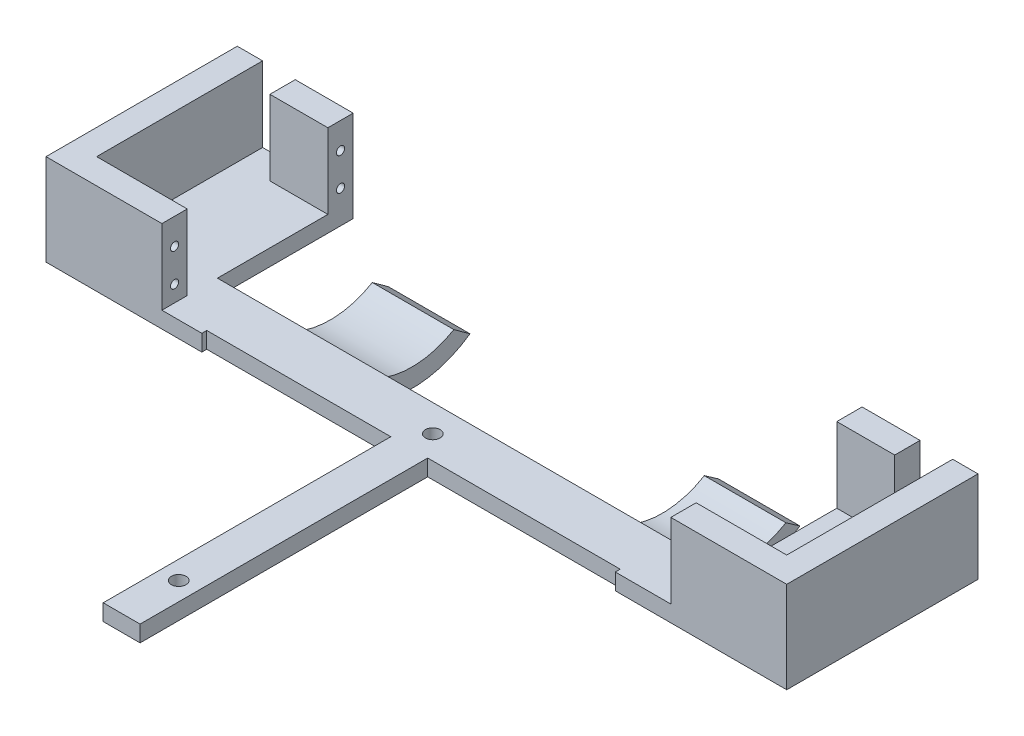
SolidWorks part; units mm, degrees
material "ABS"
ref_plane "Front" through (0, 0, 0) normal (0, 0, 1) x (1, 0, 0)
ref_plane "Top" through (0, 0, 0) normal (0, 1, 0) x (1, 0, 0)
ref_plane "Right" through (0, 0, 0) normal (1, 0, 0) x (0, 0, -1)
sketch "Sketch5" plane through (0, 0, 0) normal (0, 1, 0) x (1, 0, 0)
  line L0 (0, 0) -> (0, 88.14)
  line L1 (0, 88.14) -> (-56.41, 88.14)
  line L2 (-56.41, 88.14) -> (-56.41, 86.64)
  line L3 (-56.41, 86.64) -> (-96.41, 86.64)
  line L4 (-96.41, 86.64) -> (-96.41, 145.26)
  line L5 (-96.41, 145.26) -> (-56.41, 145.26)
  line L6 (-56.41, 145.26) -> (-56.41, 103.66)
  line L7 (-56.41, 103.66) -> (9.075, 103.66)
  line L10 (0, 0) -> (11.3, 0)
  line L11 (11.3, 0) -> (11.3, 88.14)
  line L12 (11.3, 88.14) -> (70.3, 88.14)
  line L13 (70.3, 88.14) -> (70.3, 86.64)
  line L14 (70.3, 86.64) -> (115.07, 86.64)
  line L15 (115.07, 86.64) -> (115.07, 145.26)
  line L16 (115.07, 145.26) -> (70.3, 145.26)
  line L17 (70.3, 145.26) -> (70.3, 103.66)
  line L18 (70.3, 103.66) -> (9.075, 103.66)
  dimension "D2" = 88.14
  dimension "D3" = 40
  dimension "D4" = 58.62
  dimension "D5" = 15.52
  dimension "D6" = 1.5
  dimension "D7" = 59
  dimension "D8" = 44.77
  dimension "D9" = 58.62
  dimension "D10" = 1.5
  dimension "D11" = 11.3
  dimension "D12" = 56.41
extrude "Boss-Extrude1" add sketch "Sketch5" along normal blind 5
sketch "Sketch6" plane through (0, 5, 0) normal (0, 1, 0) x (1, 0, 0)
  line L0 (-96.41, 137.5) -> (-94.6, 137.5)
  line L1 (-96.41, 145.26) -> (-96.41, 86.64) construction
  line L2 (-94.6, 137.5) -> (-94.6, 145.26)
  line L3 (-56.41, 145.26) -> (-96.41, 145.26) construction
  line L4 (-94.6, 145.26) -> (-96.41, 145.26)
  line L5 (-96.41, 145.26) -> (-96.41, 137.5)
  line L6 (-87.41, 145.26) -> (-87.41, 137.5)
  line L7 (-87.41, 137.5) -> (-68.65, 137.5)
  line L9 (-68.65, 137.5) -> (-68.65, 145.26)
  line L10 (-68.65, 145.26) -> (-87.41, 145.26)
  point P14 (-94.6, 141.38)
  dimension "D1" = 7.76
  dimension "D2" = 1.81
  dimension "D3" = 7.19
  dimension "D4" = 18.76
  dimension "D5" = 7.76
extrude "Boss-Extrude2" add sketch "Sketch6" along normal blind 28
sketch "Sketch7" plane through (-94.6, 0, 0) normal (1, 0, 0) x (0, 0, -1)
  line L0 (145.26, 33) -> (145.26, 5) construction
  line L1 (137.5, 33) -> (145.26, 33)
  line L2 (137.5, 33) -> (137.5, 28)
  line L3 (137.5, 28) -> (145.26, 28)
  line L4 (145.26, 33) -> (145.26, 28)
  dimension "D1" = 5
extrude "Boss-Extrude3" add sketch "Sketch7" along normal up to next
sketch "Sketch9" plane through (0, 0, -145.26) normal (0, 0, -1) x (-1, 0, 0)
  line L0 (96.41, 33) -> (96.41, 0) construction
  line L1 (68.65, 33) -> (96.41, 33)
  line L2 (68.65, 33) -> (68.65, 28)
  line L3 (68.65, 28) -> (96.41, 28)
  line L4 (96.41, 33) -> (96.41, 28)
extrude "Boss-Extrude4" add sketch "Sketch9" against normal up to surface (58.62 mm away) up to face at (-76.41, 2.5, -86.64)
sketch "Sketch10" plane through (0, 28, 0) normal (0, -1, 0) x (1, 0, 0)
  line L0 (-68.65, -86.64) -> (-68.65, -137.5) construction
  line L1 (-96.41, -86.64) -> (-68.65, -86.64)
  line L2 (-96.41, -86.64) -> (-96.41, -94.4)
  line L3 (-96.41, -94.4) -> (-68.65, -94.4)
  line L4 (-68.65, -86.64) -> (-68.65, -94.4)
  dimension "D1" = 7.76
extrude "Boss-Extrude5" add sketch "Sketch10" along normal up to next
sketch "Sketch11" plane through (-96.41, 0, 0) normal (-1, 0, 0) x (0, 0, 1)
  line L1 (-86.64, 0) -> (-145.26, 0)
  line L2 (-86.64, 0) -> (-86.64, 33)
  line L3 (-86.64, 33) -> (-145.26, 33)
  line L4 (-145.26, 0) -> (-145.26, 33)
extrude "Boss-Extrude6" add sketch "Sketch11" along normal blind 7.76
sketch "Sketch12" plane through (0, 5, 0) normal (0, 1, 0) x (1, 0, 0)
  line L0 (0, 0) -> (11.3, 0) construction
  line L1 (0, 88.14) -> (0, 0) construction
  circle A0 centre (5.65, 17.48) radius 2.25
  circle A1 centre (5.65, 95.35) radius 2.25
  dimension "D1" = 4.5
  dimension "D2" = 4.5
  dimension "D5" = 5.65
  dimension "D3" = 17.48
  dimension "D4" = 95.35
extrude "Cut-Extrude1" cut sketch "Sketch12" against normal through all
sketch "Sketch13" plane through (0, 5, 0) normal (0, 1, 0) x (1, 0, 0)
  line L0 (115.07, 145.26) -> (70.3, 145.26) construction
  line L1 (115.07, 145.26) -> (113.26, 145.26)
  line L2 (115.07, 145.26) -> (115.07, 137.5)
  line L3 (115.07, 137.5) -> (113.26, 137.5)
  line L4 (113.26, 145.26) -> (113.26, 137.5)
  line L5 (106.07, 145.26) -> (87.31, 145.26)
  line L6 (106.07, 145.26) -> (106.07, 137.5)
  line L7 (106.07, 137.5) -> (87.31, 137.5)
  line L8 (87.31, 145.26) -> (87.31, 137.5)
  dimension "D1" = 1.81
  dimension "D2" = 7.19
  dimension "D3" = 18.76
  dimension "D4" = 7.76
  dimension "D5" = 7.76
extrude "Boss-Extrude7" add sketch "Sketch13" along normal blind 28
sketch "Sketch14" plane through (113.26, 0, 0) normal (-1, 0, 0) x (0, 0, 1)
  line L0 (-137.5, 33) -> (-137.5, 5) construction
  line L1 (-145.26, 33) -> (-137.5, 33)
  line L2 (-145.26, 33) -> (-145.26, 28)
  line L3 (-145.26, 28) -> (-137.5, 28)
  line L4 (-137.5, 33) -> (-137.5, 28)
  dimension "D1" = 5
extrude "Boss-Extrude8" add sketch "Sketch14" along normal up to next
sketch "Sketch15" plane through (0, 0, -137.5) normal (0, 0, 1) x (1, 0, 0)
  line L0 (115.07, 33) -> (115.07, 5) construction
  line L1 (87.31, 33) -> (115.07, 33)
  line L2 (87.31, 33) -> (87.31, 28)
  line L3 (87.31, 28) -> (115.07, 28)
  line L4 (115.07, 33) -> (115.07, 28)
extrude "Boss-Extrude9" add sketch "Sketch15" along normal up to surface (50.86 mm away) up to face at (92.685, 2.5, -86.64)
sketch "Sketch16" plane through (0, 28, 0) normal (0, -1, 0) x (1, 0, 0)
  line L0 (87.31, -86.64) -> (87.31, -137.5) construction
  line L1 (115.07, -86.64) -> (87.31, -86.64)
  line L2 (115.07, -86.64) -> (115.07, -94.4)
  line L3 (115.07, -94.4) -> (87.31, -94.4)
  line L4 (87.31, -86.64) -> (87.31, -94.4)
  dimension "D1" = 7.76
extrude "Boss-Extrude10" add sketch "Sketch16" along normal up to next
sketch "Sketch17" plane through (115.07, 0, 0) normal (1, 0, 0) x (0, 0, -1)
  line L0 (145.26, 33) -> (145.26, 0) construction
  line L1 (86.64, 33) -> (145.26, 33)
  line L2 (86.64, 33) -> (86.64, 0)
  line L3 (86.64, 0) -> (145.26, 0)
  line L4 (145.26, 33) -> (145.26, 0)
extrude "Boss-Extrude11" add sketch "Sketch17" along normal blind 7.76
sketch "Sketch19" plane through (0, 0, -103.66) normal (0, 0, -1) x (-1, 0, 0)
  line L1 (-42.905, 8) -> (27.305, 8)
  line L2 (-42.905, 8) -> (-42.905, 0)
  line L3 (-42.905, 0) -> (27.305, 0)
  line L4 (27.305, 8) -> (27.305, 0)
  line L5 (-70.3, 0) -> (56.41, 0) construction
  line L7 (-70.3, 5) -> (-70.3, 0) construction
  dimension "D1" = 70.21
  dimension "D2" = 27.395
  dimension "D3" = 8
extrude "Boss-Extrude12" [suppressed] add sketch "Sketch19" along normal blind 9.2
sketch "Sketch20" [suppressed] plane through (-27.305, 0, 0) normal (-1, 0, 0) x (0, 0, 1)
  line L0 (-112.86, 5) -> (-127.36, 5) construction
  line L1 (-112.86, 0) -> (-137.8238, 0) construction
  line L2 (-127.36, 5) -> (-127.36, 15.5) construction
  line L5 (-112.86, 8) -> (-127.36, 8) construction
  line L6 (-112.86, 8) -> (-112.86, 3)
  line L7 (-112.86, 0) -> (-112.86, 8) construction
  line L8 (-137.2829, -0.8718) -> (-134.86, 1)
  arc A5 (-112.86, 8) -> (-134.86, 1) centre (-127.36, 15.5) cw
  arc A6 (-112.86, 3) -> (-137.2829, -0.8718) centre (-127.36, 15.5) cw
  dimension "D1" = 14.5
  dimension "D2" = 10.5
sketch "Sketch23" plane through (0, 0, -145.26) normal (0, 0, -1) x (-1, 0, 0)
  line L0 (-87.31, 33) -> (-87.31, 5) construction
  line L1 (-122.83, 33) -> (-87.31, 33)
  line L2 (-122.83, 33) -> (-122.83, 28)
  line L3 (-122.83, 28) -> (-87.31, 28)
  line L4 (-87.31, 33) -> (-87.31, 28)
extrude "Cut-Extrude4" cut sketch "Sketch23" against normal up to next
sketch "Sketch24" plane through (0, 0, -145.26) normal (0, 0, -1) x (-1, 0, 0)
  line L0 (104.17, 33) -> (104.17, 0) construction
  line L1 (68.65, 33) -> (104.17, 33)
  line L2 (68.65, 33) -> (68.65, 28)
  line L3 (68.65, 28) -> (104.17, 28)
  line L4 (104.17, 33) -> (104.17, 28)
extrude "Cut-Extrude5" cut sketch "Sketch24" against normal up to next
sketch "Sketch25" plane through (-94.6, 0, 0) normal (1, 0, 0) x (0, 0, -1)
  line L1 (145.26, 28) -> (137.5, 28)
  line L2 (145.26, 28) -> (145.26, 5)
  line L3 (145.26, 5) -> (137.5, 5)
  line L4 (137.5, 28) -> (137.5, 5)
extrude "Cut-Extrude6" cut sketch "Sketch25" against normal up to surface (1.81 mm away) up to face at (-96.41, 16.5, -115.95)
sketch "Sketch26" plane through (113.26, 0, 0) normal (-1, 0, 0) x (0, 0, 1)
  line L1 (-145.26, 28) -> (-137.5, 28)
  line L2 (-145.26, 28) -> (-145.26, 5)
  line L3 (-145.26, 5) -> (-137.5, 5)
  line L4 (-137.5, 28) -> (-137.5, 5)
extrude "Cut-Extrude7" cut sketch "Sketch26" against normal up to surface (1.81 mm away) up to face at (115.07, 16.5, -115.95)
sketch "Sketch27" plane through (-68.65, 0, 0) normal (1, 0, 0) x (0, 0, -1)
  line L0 (145.26, 28) -> (145.26, 5) construction
  line L1 (137.5, 5) -> (145.26, 5) construction
  line L2 (86.64, 5) -> (94.4, 5) construction
  line L3 (94.4, 5) -> (94.4, 28) construction
  circle A0 centre (141.38, 10) radius 1.25
  circle A1 centre (141.38, 20) radius 1.25
  circle A2 centre (90.52, 10) radius 1.25
  circle A3 centre (90.52, 20) radius 1.25
  dimension "D3" = 2.5
  dimension "D4" = 2.5
  dimension "D7" = 2.5
  dimension "D8" = 2.5
  dimension "D11" = 3.88
  dimension "D12" = 3.88
  dimension "D1" = 3.88
  dimension "D2" = 3.88
  dimension "D5" = 5
  dimension "D6" = 15
  dimension "D9" = 5
  dimension "D10" = 15
extrude "Cut-Extrude8" cut sketch "Sketch27" against normal blind 5
sketch "Sketch28" plane through (87.31, 0, 0) normal (-1, 0, 0) x (0, 0, 1)
  line L0 (-94.4, 5) -> (-86.64, 5) construction
  line L1 (-94.4, 5) -> (-94.4, 28) construction
  line L2 (-145.26, 28) -> (-145.26, 5) construction
  line L3 (-145.26, 5) -> (-137.5, 5) construction
  circle A0 centre (-90.52, 10) radius 1.25
  circle A1 centre (-90.52, 20) radius 1.25
  circle A2 centre (-141.38, 10) radius 1.25
  circle A3 centre (-141.38, 20) radius 1.25
  dimension "D1" = 2.5
  dimension "D2" = 2.5
  dimension "D5" = 3.88
  dimension "D7" = 3.88
  dimension "D8" = 2.5
  dimension "D9" = 2.5
  dimension "D11" = 5
  dimension "D12" = 3.88
  dimension "D3" = 5
  dimension "D4" = 15
  dimension "D6" = 3.88
  dimension "D10" = 15
extrude "Cut-Extrude9" cut sketch "Sketch28" against normal blind 5
extrude "Boss-Extrude13" [suppressed] add sketch "Sketch20" against normal up to vertex
fillet "Fillet1" [suppressed] radius 15
sketch "Sketch29" plane through (70.3, 0, 0) normal (-1, 0, 0) x (0, 0, 1)
  line L0 (-103.66, 5) -> (-103.66, 13.5) construction
  line L1 (-103.66, 13.5) -> (-126.02, 13.5) construction
  line L4 (-100.8858, 13.5) -> (-96.02, 13.5)
  line L5 (-143.2273, -11.0746) -> (-138.9217, -8.0702)
  arc A0 (-100.8858, 13.5) -> (-138.9217, -8.0702) centre (-126.02, 13.5) cw
  arc A1 (-96.02, 13.5) -> (-143.2273, -11.0746) centre (-126.02, 13.5) cw
  dimension "D1" = 8.5
  dimension "D2" = 22.36
extrude "Boss-Extrude14" add sketch "Sketch29" along normal blind 25
sketch "Sketch30" plane through (45.3, 0, 0) normal (-1, 0, 0) x (0, 0, 1)
  line L5 (-102.3667, 5) -> (-94.699, 5)
  line L6 (-102.3667, 5) -> (-102.3667, 14.5526)
  line L7 (-102.3667, 14.5526) -> (-94.699, 14.5526)
  line L8 (-94.699, 5) -> (-94.699, 14.5526)
extrude "Cut-Extrude13" cut sketch "Sketch30" against normal blind 30
fillet "Fillet2" radius 15 1 edges at (57.8, 2.0214, -103.66)
sketch "Sketch31" plane through (0, 5, 0) normal (0, 1, 0) x (1, 0, 0)
  line L1 (70.3, 145.26) -> (75.3, 145.26)
  line L2 (70.3, 145.26) -> (70.3, 103.66)
  line L3 (70.3, 103.66) -> (75.3, 103.66)
  line L4 (75.3, 145.26) -> (75.3, 103.66)
  dimension "D1" = 5
extrude "Cut-Extrude14" cut sketch "Sketch31" against normal up to next
sketch "Sketch33" [suppressed] plane through (-56.41, 0, 0) normal (-1, 0, 0) x (0, 0, 1)
  line L0 (-103.66, 5) -> (-126.02, 5) construction
  line L1 (-126.02, 5) -> (-126.02, 14) construction
  line L2 (-100.8599, 14) -> (-95.1475, 14)
  line L3 (-143.7277, -11.2893) -> (-138.6, -7.7892)
  arc A0 (-100.8599, 14) -> (-138.6, -7.7892) centre (-126.02, 14) cw
  arc A1 (-95.1475, 14) -> (-143.7277, -11.2893) centre (-126.02, 14) cw
  dimension "D1" = 9
sketch "Sketch34" [suppressed] plane through (-56.41, 0, 0) normal (-1, 0, 0) x (0, 0, 1)
  line L1 (-102.5247, 5) -> (-93.7756, 5)
  line L2 (-102.5247, 5) -> (-102.5247, 17.8457)
  line L3 (-102.5247, 17.8457) -> (-93.7756, 17.8457)
  line L4 (-93.7756, 5) -> (-93.7756, 17.8457)
extrude "Cut-Extrude15" [suppressed] cut sketch "Sketch34" against normal blind 30
fillet "Fillet6" radius 21 1 edges at (57.8, 0, -99.2291)
sketch "Sketch35" plane through (-56.41, 0, 0) normal (1, 0, 0) x (0, 0, -1)
  line L0 (103.66, 5) -> (126.02, 5) construction
  line L1 (126.02, 5) -> (126.02, 14) construction
  line L2 (100.8599, 14) -> (95.1475, 14)
  line L3 (138.8641, -7.6347) -> (143.8177, -11.2261)
  arc A0 (95.1475, 14) -> (143.8177, -11.2261) centre (126.02, 14) ccw
  arc A1 (100.8599, 14) -> (138.8641, -7.6347) centre (126.02, 14) ccw
extrude "Boss-Extrude15" add sketch "Sketch35" along normal blind 25
fillet "Fillet7" radius 15 1 edges at (-43.91, 2.4649, -103.66)
fillet "Fillet8" radius 20 1 edges at (-43.91, 0, -98.5043)
ref_plane "Plane1" through (-31.41, 14, -100.8599) normal (0, 1, 0) x (1, 0, 0)
sketch "Sketch37" plane through (-31.41, 0, 0) normal (1, 0, 0) x (0, 0, -1)
  line L0 (100.8599, 14) -> (95.1475, 14) construction
  line L1 (95.1475, 14) -> (102.5247, 14)
  line L2 (95.1475, 14) -> (95.1475, 5)
  line L3 (95.1475, 5) -> (102.5247, 5)
  line L4 (102.5247, 14) -> (102.5247, 5)
  arc A0 (95.1475, 14) -> (96.4885, 5) centre (126.02, 14) ccw construction
extrude "Cut-Extrude16" cut sketch "Sketch37" against normal blind 25
sketch "Sketch38" plane through (0, 0, -145.26) normal (0, 0, -1) x (-1, 0, 0)
  line L1 (87.41, 28) -> (86.41, 28)
  line L2 (87.41, 28) -> (87.41, 5)
  line L3 (87.41, 5) -> (86.41, 5)
  line L4 (86.41, 28) -> (86.41, 5)
  line L5 (-106.07, 28) -> (-105.07, 28)
  line L6 (-106.07, 28) -> (-106.07, 5)
  line L7 (-106.07, 5) -> (-105.07, 5)
  line L8 (-105.07, 28) -> (-105.07, 5)
  dimension "D1" = 1
  dimension "D2" = 1
extrude "Cut-Extrude17" cut sketch "Sketch38" against normal up to next
sketch "Sketch39" plane through (0, 0, -145.26) normal (0, 0, -1) x (-1, 0, 0)
  line L0 (56.41, 0) -> (104.17, 0) construction
  line L1 (56.41, 5) -> (68.65, 5)
  line L2 (56.41, 5) -> (56.41, 0)
  line L3 (56.41, 0) -> (68.65, 0)
  line L4 (68.65, 5) -> (68.65, 0)
  line L6 (-87.31, 5) -> (-75.3, 5)
  line L7 (-87.31, 5) -> (-87.31, 0)
  line L8 (-87.31, 0) -> (-75.3, 0)
  line L9 (-75.3, 5) -> (-75.3, 0)
extrude "Cut-Extrude19" cut sketch "Sketch39" against normal up to surface (41.6 mm away) up to face at (72.8, 2.5, -103.66)
ref_plane "Plane2" through (5.65, 0, 0) normal (-1, 0, 0) x (0, 0, 1)
